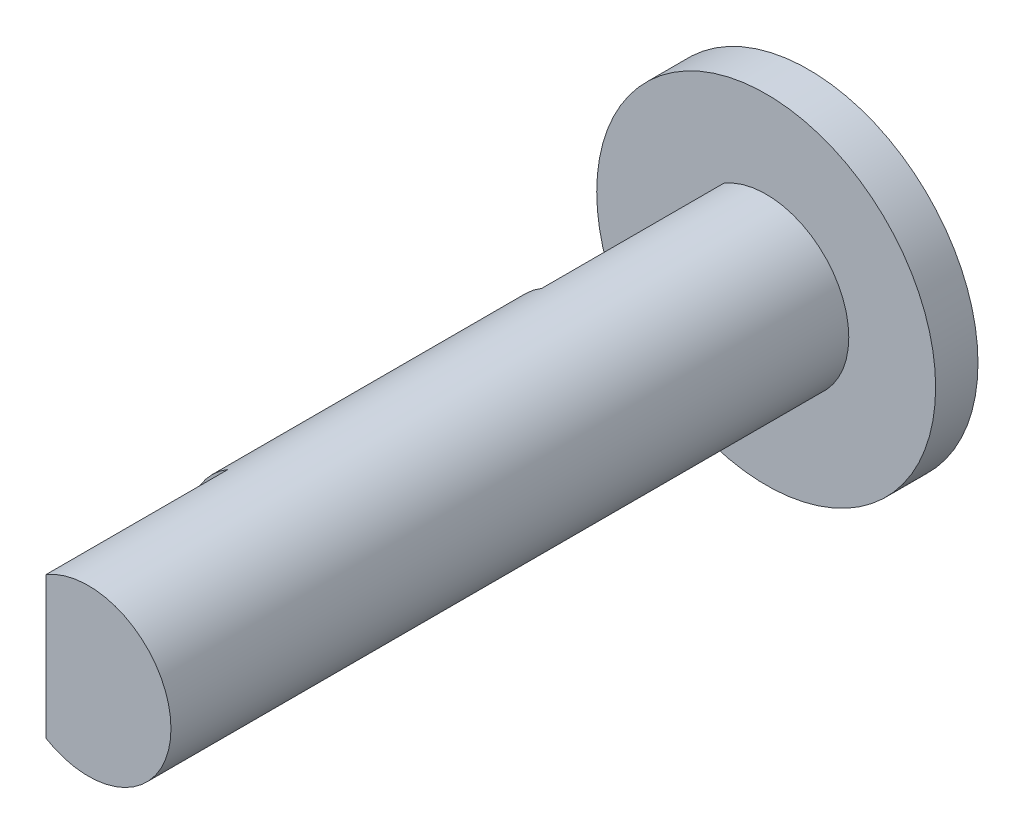
SolidWorks part; units mm, degrees
ref_plane "Front Plane" through (0, 0, 0) normal (0, 0, 1) x (1, 0, 0)
ref_plane "Top Plane" through (0, 0, 0) normal (0, 1, 0) x (1, 0, 0)
ref_plane "Right Plane" through (0, 0, 0) normal (1, 0, 0) x (0, 0, -1)
sketch "Sketch2" plane through (0, 0, 0) normal (0, 0, 1) x (1, 0, 0)
  circle A0 centre (0, 0) radius 1.95
  dimension "D1" = 3.9
extrude "Boss-Extrude1" add sketch "Sketch2" along normal mid plane 16
sketch "Sketch4" plane through (0, 0, -8) normal (0, 0, -1) x (-1, 0, 0)
  line L0 (1, 1.6741) -> (1, -1.6741)
  arc A0 (1, -1.6741) -> (1, 1.6741) centre (0, 0) ccw
  dimension "D2" = 3.9
  dimension "D1" = 1
extrude "Cut-Extrude1" cut sketch "Sketch4" against normal blind 4.3
mirror "Mirror1" about plane through (0, 0, 0) normal (0, 0, 1) of "Cut-Extrude1"
ref_plane "Plane1" through (0, 0, -8) normal (0, 0, -1) x (-1, 0, 0)
sketch "Sketch5" plane through (0, 0, -8) normal (0, 0, -1) x (-1, 0, 0)
  circle A0 centre (0, 0) radius 4
  dimension "D1" = 8
extrude "Boss-Extrude2" add sketch "Sketch5" along normal blind 1
